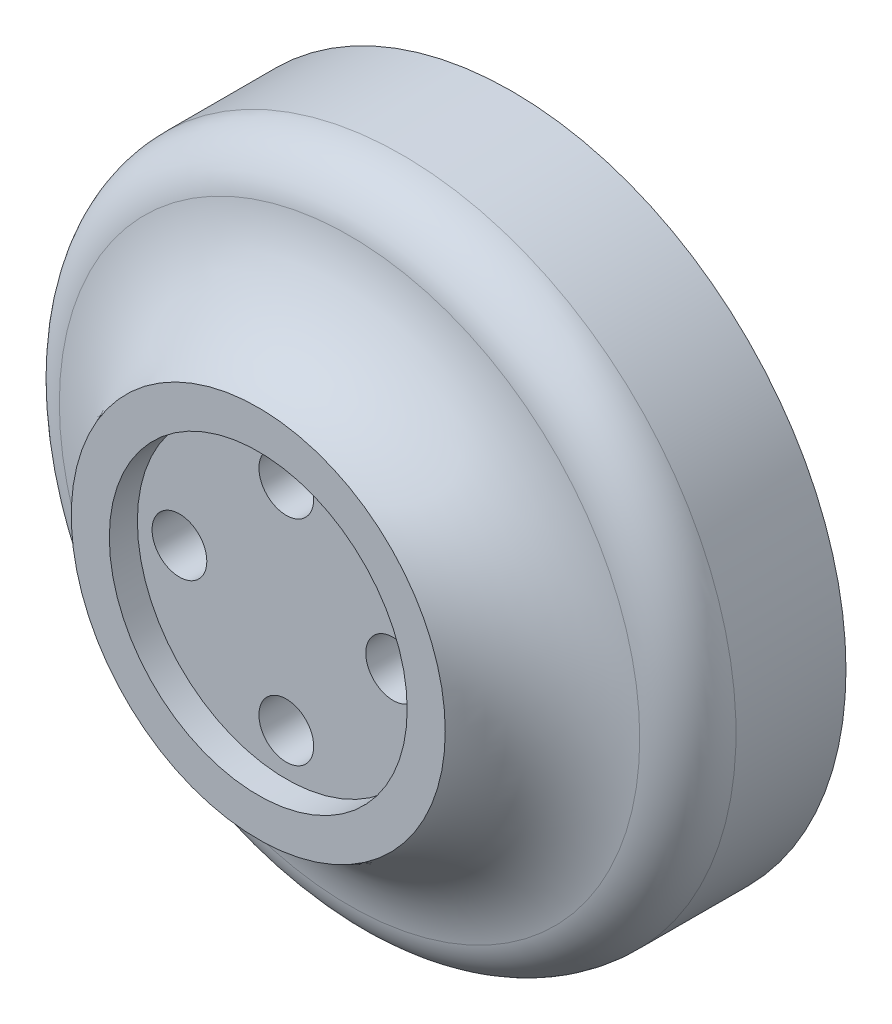
SolidWorks part; units mm, degrees
ref_plane "Front Plane" through (0, 0, 0) normal (0, 0, 1) x (1, 0, 0)
ref_plane "Top Plane" through (0, 0, 0) normal (0, 1, 0) x (1, 0, 0)
ref_plane "Right Plane" through (0, 0, 0) normal (1, 0, 0) x (0, 0, -1)
sketch "Sketch1" plane through (0, 0, 0) normal (0, 0, 1) x (1, 0, 0)
  circle A0 centre (0, 0) radius 25
  dimension "D1" = 50
extrude "Boss-Extrude1" add sketch "Sketch1" along normal blind 12
sketch "Sketch2" plane through (0, 0, 0) normal (0, 0, 1) x (1, 0, 0)
  circle A0 centre (0, 0) radius 14
  dimension "D1" = 28
extrude "Boss-Extrude2" add sketch "Sketch2" along normal blind 7 from surface starting at face at (25, 0, 12)
sketch "Sketch3" plane through (0, 0, 0) normal (0, 0, 1) x (1, 0, 0)
  circle A0 centre (0, 0) radius 11.15
  dimension "D1" = 22.3
extrude "Cut-Extrude1" cut sketch "Sketch3" against normal blind 2.1 from surface starting at face at (14, 0, 19)
fillet "Fillet1" radius 10 1 edges at (14, 0, 12)
fillet "Fillet2" radius 4 1 edges at (25, 0, 12)
sketch "Sketch4" plane through (0, 0, 0) normal (0, 0, 1) x (1, 0, 0)
  circle A0 centre (0, 0) radius 11
  dimension "D1" = 22
extrude "Boss-Extrude3" add sketch "Sketch4" against normal blind 8
sketch "Sketch5" plane through (0, 0, 0) normal (0, 0, 1) x (1, 0, 0)
  line L0 (0, -12.65) -> (0, 12.65) construction
  line L1 (12.65, 0) -> (-12.65, 0) construction
  circle A0 centre (0, 8) radius 2.05
  circle A1 centre (8, 0) radius 2.05
  circle A2 centre (0, -8) radius 2.05
  circle A3 centre (-8, 0) radius 2.05
  dimension "D5" = 4.1
  dimension "D1" = 8
  dimension "D2" = 8
  dimension "D3" = 8
  dimension "D4" = 8
extrude "Cut-Extrude2" cut sketch "Sketch5" against normal blind 9 from surface starting at face at (11.15, 0, 16.9)
sketch "Sketch6" plane through (0, 0, 0) normal (0, 0, 1) x (1, 0, 0)
  line L0 (0, -12.65) -> (0, 12.65) construction
  line L1 (12.65, 0) -> (-12.65, 0) construction
  circle A0 centre (0, 18) radius 2.05
  circle A1 centre (18, 0) radius 2.05
  circle A2 centre (0, -18) radius 2.05
  circle A3 centre (-18, 0) radius 2.05
  point P12 (0, 0)
  dimension "D5" = 4.1
  dimension "D1" = 18
  dimension "D2" = 18
  dimension "D3" = 18
  dimension "D4" = 18
extrude "Cut-Extrude3" cut sketch "Sketch6" along normal blind 9
